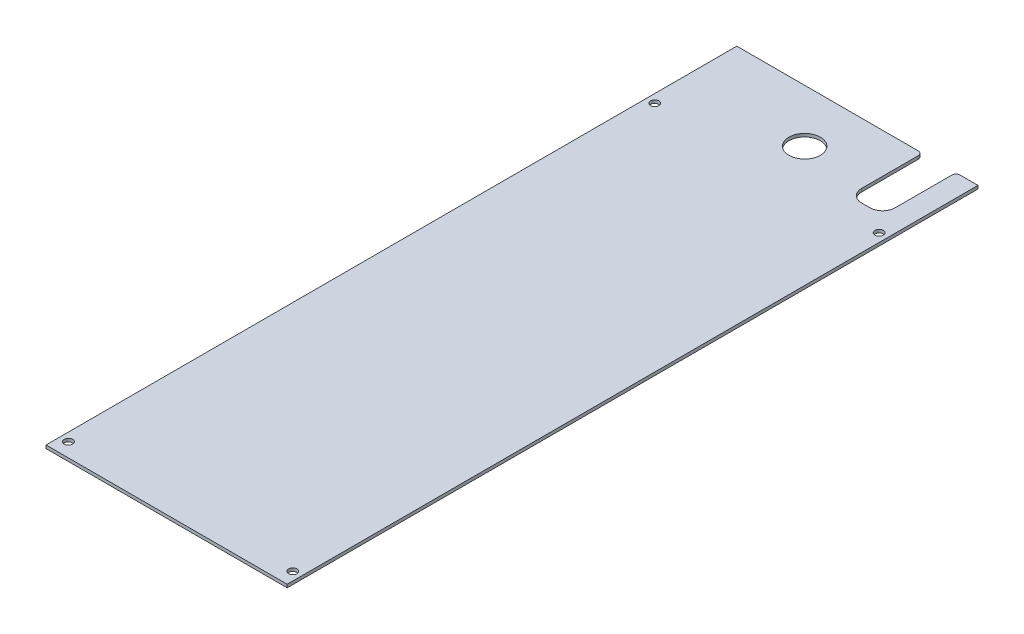
SolidWorks part; units mm, degrees
note: The reader was unsure of these and kept them because the rebuilt part matched: thickness of "Brida base2", "Chapa metálica(12)", "Chapa metálica(21)", "Chapa metálica(22)", "Chapa metálica(23)".
material "Poliestireno"
ref_plane "Alzado" through (0, 0, 0) normal (0, 0, 1) x (1, 0, 0)
ref_plane "Planta" through (0, 0, 0) normal (0, 1, 0) x (1, 0, 0)
ref_plane "Vista lateral" through (0, 0, 0) normal (1, 0, 0) x (0, 0, -1)
sketch "Croquis12" plane through (0, 0, 0) normal (0, 1, 0) x (1, 0, 0)
  line L0 (0, 0) -> (0, 121.41) construction
  line L1 (-57.5, -207.99) -> (57.5, -207.99)
  line L2 (-57.5, -207.99) -> (-57.5, 121.41)
  line L3 (-57.5, 121.41) -> (57.5, 121.41)
  line L4 (57.5, -207.99) -> (57.5, 121.41)
  point P14 (57.5, 121.41)
  point P17 (-57.5, 121.41)
  dimension "D1" = 115
  dimension "D2" = 207.99
  dimension "D3" = 121.41
base flange "Brida base2" sketch "Croquis12" thickness 1.5 reverse thickness direction no parameters "D1"=1
sketch "Croquis25" plane through (0, 0, 0) normal (0, 1, 0) x (1, 0, 0)
  line L0 (0, 0) -> (0, -48.7685) construction
  line L2 (-159.058, -201.3) -> (150.1867, -201.3) construction
  dimension "D2" = 201.3
sketch "Croquis27" plane through (0, 0, 0) normal (0, 1, 0) x (1, 0, 0)
  line L0 (0, 0) -> (0, -88.775) construction
  line L1 (-159.058, -201.3) -> (150.1867, -201.3) construction
  circle A0 centre (-53.5, -201.3) radius 2
  circle A1 centre (-53.5, 78.26) radius 2
  circle A2 centre (53.5, 78.26) radius 2
  circle A3 centre (53.5, -201.3) radius 2
  dimension "D1" = 4
  dimension "D4" = 107
  dimension "D2" = 78.26
extrude "Cortar-Extruir6" cut sketch "Croquis27" against normal up to next normal cut yes
sketch "Croquis28" plane through (0, 0, 0) normal (0, 1, 0) x (1, 0, 0)
  line L1 (-57.5, -207.99) -> (57.5, -207.99) construction
  circle A0 centre (0, 96.25) radius 7.5
  dimension "D1" = 304.24
  dimension "D2" = 15
extrude "Cortar-Extruir7" cut sketch "Croquis28" against normal up to next normal cut yes
sketch "Croquis29" plane through (0, 0, 0) normal (0, 1, 0) x (1, 0, 0)
  line L0 (39, 86.41) -> (39, 125.7663) construction
  line L1 (31, 121.41) -> (47, 121.41)
  line L2 (31, 121.41) -> (31, 86.41)
  line L3 (31, 86.41) -> (47, 86.41)
  line L4 (47, 121.41) -> (47, 86.41)
  line L5 (57.5, 121.41) -> (-57.5, 121.41) construction
  circle A0 centre (0, 96.25) radius 7.5 construction
  dimension "D1" = 39
  dimension "D2" = 16
  dimension "D3" = 35
extrude "Cortar-Extruir8" cut sketch "Croquis29" against normal through all normal cut yes
fillet "Redondeo1" radius 6 2 edges at (47, -0.75, -86.41) (31, -0.75, -86.41)
fillet "Redondeo2" radius 2 2 edges at (47, -0.75, -121.41) (31, -0.75, -121.41)
sketch "Líneas de pliegue3" plane through (0, 0, 0) normal (0, 1, 0) x (1, 0, 0)
sketch "Cuadro delimitador3" plane through (0, 0, 0) normal (0, 1, 0) x (1, 0, 0)
sheet metal parameters "Chapa metálica(12)" thickness 1.5 parameters "D1"=1
flat pattern "Chapa desplegada(12)" [suppressed]
sketch "Líneas de pliegue4" plane through (0, 0, 0) normal (0, 1, 0) x (1, 0, 0)
sketch "Cuadro delimitador4" [suppressed] plane through (0, 0, 0) normal (0, 1, 0) x (1, 0, 0)
sheet metal parameters "Chapa metálica(21)" thickness 1.5 parameters "D1"=1, "D7"=3
flat pattern "Chapa desplegada(12)"
sketch "Líneas de pliegue4" plane through (0, 0, 0) normal (0, 1, 0) x (1, 0, 0)
sketch "Cuadro delimitador4" [suppressed] plane through (0, 0, 0) normal (0, 1, 0) x (1, 0, 0)
sheet metal parameters "Chapa metálica(22)" thickness 1.5 parameters "D1"=1, "D7"=3
flat pattern "Chapa desplegada(12)"
sketch "Líneas de pliegue4" plane through (0, 0, 0) normal (0, 1, 0) x (1, 0, 0)
sketch "Cuadro delimitador4" [suppressed] plane through (0, 0, 0) normal (0, 1, 0) x (1, 0, 0)
sheet metal parameters "Chapa metálica(23)" thickness 1.5 parameters "D1"=1, "D7"=3
flat pattern "Chapa desplegada(12)"
sketch "Líneas de pliegue4" plane through (0, 0, 0) normal (0, 1, 0) x (1, 0, 0)
sketch3d "Cuadro delimitador4" [suppressed]
  line L0 (-57.5, -207.99, 0) -> (-57.5, 121.41, 0) construction
  line L1 (57.5, -207.99, 0) -> (57.5, 121.41, 0) construction
  line L2 (-57.5, -207.99, 0) -> (57.5, -207.99, 0) construction
  line L3 (-57.5, 121.41, 0) -> (57.5, 121.41, 0) construction
